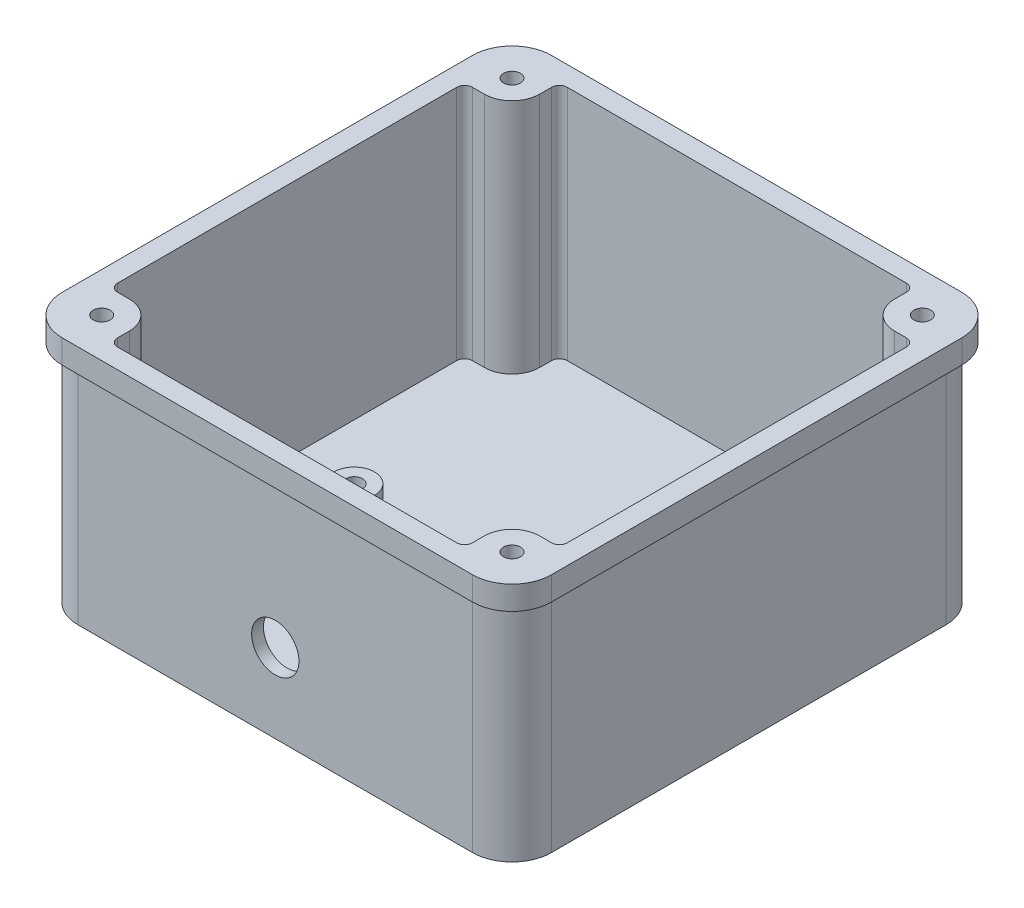
SolidWorks part; units mm, degrees
ref_plane "Front Plane" through (0, 0, 0) normal (0, 0, 1) x (1, 0, 0)
ref_plane "Top Plane" through (0, 0, 0) normal (0, 1, 0) x (1, 0, 0)
ref_plane "Right Plane" through (0, 0, 0) normal (1, 0, 0) x (0, 0, -1)
sketch "Sketch1" plane through (0, 0, 0) normal (0, 1, 0) x (1, 0, 0)
  line L1 (-60, 60) -> (60, 60)
  line L2 (-60, 60) -> (-60, -60)
  line L3 (-60, -60) -> (60, -60)
  line L4 (60, 60) -> (60, -60)
  line L5 (-60, 60) -> (60, -60) construction
  line L6 (-60, -60) -> (60, 60) construction
  point P0 (0, 0)
  dimension "D1" = 120
  dimension "D2" = 120
extrude "Boss-Extrude1" add sketch "Sketch1" along normal blind 63
shell "Shell1" thickness 3 removed face at (0, 63, 0)
sketch "Sketch2" plane through (0, 3, 0) normal (0, 1, 0) x (1, 0, 0)
  line L0 (0, 60) -> (0, -60) construction
  line L1 (60, 60) -> (-60, 60) construction
  line L2 (-60, -60) -> (60, -60) construction
  line L3 (-60, 0) -> (60, 0) construction
  line L4 (-60, 60) -> (-60, -60) construction
  line L5 (60, -60) -> (60, 60) construction
  line L6 (-60, 52) -> (-52, 52) construction
  line L7 (-52, 52) -> (-52, 60) construction
  line L21 (-52, -52) -> (-52, -60) construction
  line L22 (-60, -52) -> (-52, -52) construction
  line L36 (52, 44.98) -> (55, 44.98)
  line L41 (44.98, 52) -> (44.98, 55)
  line L43 (-44.98, 52) -> (-44.98, 55)
  line L44 (-52, 44.98) -> (-55, 44.98)
  line L45 (-57, 42.98) -> (-57, 57)
  line L46 (-57, 57) -> (-42.98, 57)
  line L47 (57, 57) -> (42.98, 57)
  line L48 (57, 42.98) -> (57, 57)
  line L49 (57, -42.98) -> (57, -57)
  line L50 (57, -57) -> (42.98, -57)
  line L51 (44.98, -52) -> (44.98, -55)
  line L52 (52, -44.98) -> (55, -44.98)
  line L53 (-52, -44.98) -> (-55, -44.98)
  line L54 (-44.98, -52) -> (-44.98, -55)
  line L55 (-57, -57) -> (-42.98, -57)
  line L56 (-57, -42.98) -> (-57, -57)
  circle A0 centre (-52, 52) radius 2.15
  arc A1 (-52, 44.98) -> (-44.98, 52) centre (-52, 52) ccw
  circle A2 centre (-52, 52) radius 7.02 construction
  circle A5 centre (52, 52) radius 2.15
  circle A12 centre (52, -52) radius 2.15
  circle A16 centre (-52, -52) radius 2.15
  arc A19 (-57, 42.98) -> (-55, 44.98) centre (-55, 42.98) cw
  arc A20 (-42.98, 57) -> (-44.98, 55) centre (-42.98, 55) ccw
  arc A21 (57, 42.98) -> (55, 44.98) centre (55, 42.98) ccw
  arc A22 (52, 44.98) -> (44.98, 52) centre (52, 52) cw
  arc A23 (42.98, 57) -> (44.98, 55) centre (42.98, 55) cw
  arc A24 (42.98, -57) -> (44.98, -55) centre (42.98, -55) ccw
  arc A25 (52, -44.98) -> (44.98, -52) centre (52, -52) ccw
  arc A26 (57, -42.98) -> (55, -44.98) centre (55, -42.98) cw
  arc A27 (-57, -42.98) -> (-55, -44.98) centre (-55, -42.98) ccw
  arc A28 (-52, -44.98) -> (-44.98, -52) centre (-52, -52) cw
  arc A29 (-42.98, -57) -> (-44.98, -55) centre (-42.98, -55) cw
  dimension "D1" = 8
  dimension "D4" = 4.3
  dimension "D3" = 2
  dimension "D2" = 8
extrude "Boss-Extrude2" add sketch "Sketch2" along normal blind 60
sketch "Sketch3" plane through (0, 63, 0) normal (0, 1, 0) x (1, 0, 0)
  line L0 (-60, -60) -> (60, -60) construction
  line L1 (60, -60) -> (60, 60) construction
  line L2 (-60, 60) -> (-60, -60) construction
  line L3 (60, 60) -> (-60, 60) construction
  line L4 (-60, -60) -> (60, -60)
  line L5 (60, -60) -> (60, 60)
  line L6 (-60, 60) -> (-60, -60)
  line L7 (60, 60) -> (-60, 60)
  line L8 (62, 62) -> (-62, 62)
  line L9 (-62, 62) -> (-62, -62)
  line L10 (-62, -62) -> (62, -62)
  line L11 (62, -62) -> (62, 62)
  dimension "D1" = 2
extrude "Boss-Extrude3" add sketch "Sketch3" against normal blind 6
fillet "Fillet1" radius 10 8 edges at (62, 60, 62) (60, 28.5, 60) (62, 60, -62) (60, 28.5, -60) (-62, 60, -62) (-60, 28.5, -60) (-62, 60, 62) (-60, 28.5, 60)
sketch "Sketch4" plane through (0, 3, 0) normal (0, 1, 0) x (1, 0, 0)
  line L0 (-62, 0) -> (62, 0) construction
  line L1 (-62, 52) -> (-62, -52) construction
  line L2 (62, -52) -> (62, 52) construction
  line L4 (52, 62) -> (-52, 62) construction
  line L5 (0, 62) -> (0, -62) construction
  line L6 (-52, -62) -> (52, -62) construction
  circle A0 centre (-40, 0) radius 2.15
  circle A1 centre (40, 0) radius 2.15
  dimension "D1" = 4.3
  dimension "D2" = 80
extrude "Cut-Extrude1" cut sketch "Sketch4" against normal blind 3
sketch "Sketch5" plane through (0, 3, 0) normal (0, 1, 0) x (1, 0, 0)
  line L0 (0, 62) -> (0, -62) construction
  line L1 (52, 62) -> (-52, 62) construction
  line L2 (-52, -62) -> (52, -62) construction
  circle A0 centre (-40, 0) radius 2.15 construction
  circle A1 centre (-40, 0) radius 2.15
  circle A2 centre (-40, 0) radius 5.15
  circle A3 centre (40, 0) radius 2.15
  circle A4 centre (40, 0) radius 5.15
  dimension "D1" = 3
extrude "Boss-Extrude4" add sketch "Sketch5" along normal blind 3
sketch "Sketch6" plane through (0, 0, 60) normal (0, 0, 1) x (1, 0, 0)
  line L0 (0, 20) -> (0, 0) construction
  circle A0 centre (0, 20) radius 6
  dimension "D1" = 12
  dimension "D2" = 20
extrude "Cut-Extrude2" cut sketch "Sketch6" against normal blind 10
other "CPoint1" parameters "Diameter"=3, "StubLength"=4.5
ref_axis "Axis1" through (0, 20, 70) along (0, 0, -1)
